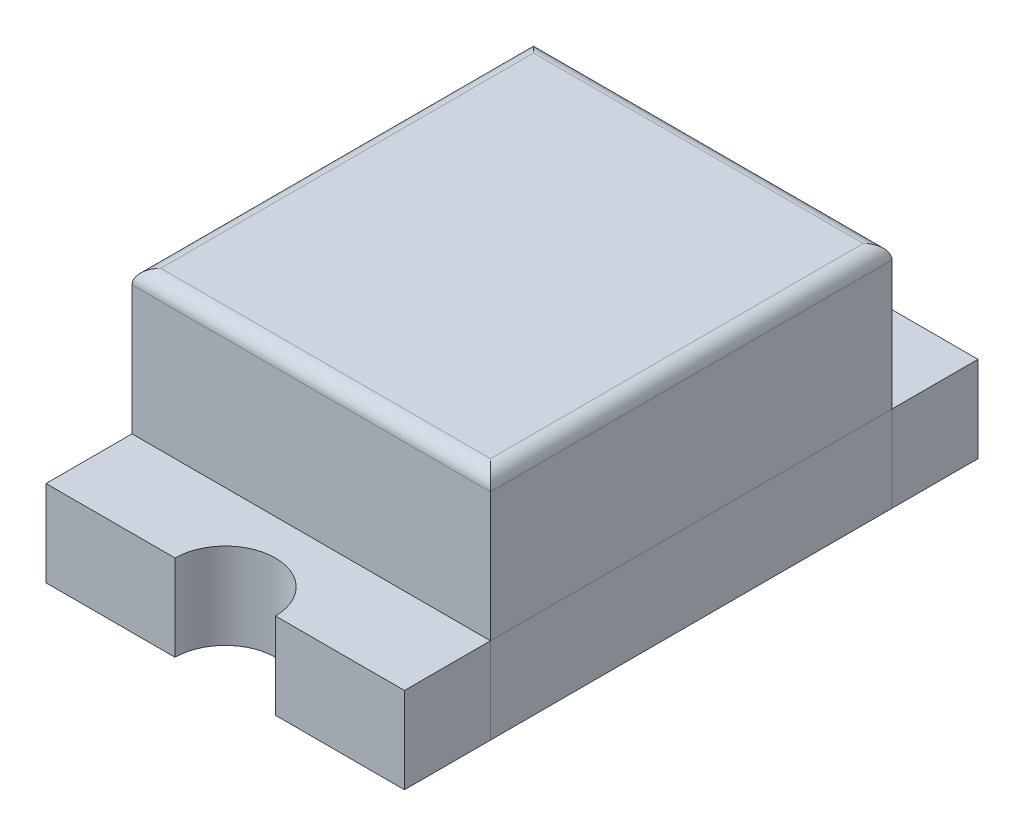
SolidWorks part; units mm, degrees
other "Saliente-Extruir4"
ref_plane "Alzado" through (0, 0, 0) normal (0, 0, 1) x (1, 0, 0)
ref_plane "Planta" through (0, 0, 0) normal (0, 1, 0) x (1, 0, 0)
ref_plane "Vista lateral" through (0, 0, 0) normal (1, 0, 0) x (0, 0, -1)
sketch "Croquis1" plane through (0, 0, 0) normal (0, 1, 0) x (1, 0, 0)
  line L0 (-0.8495, 0.7) -> (0.995, 0.7)
  line L1 (0.625, 1) -> (-0.625, 1)
  line L2 (0.625, 1) -> (0.625, -1)
  line L3 (0.625, -1) -> (-0.625, -1)
  line L4 (-0.625, 1) -> (-0.625, -1)
  line L5 (-0.8495, -0.7) -> (0.995, -0.7)
  circle A0 centre (0, 1) radius 0.175
  circle A1 centre (0, -1) radius 0.175
  point P0 (0, 0)
  point P14 (0, 0)
  dimension "D5" = 0.35
  dimension "D1" = 2
  dimension "D2" = 1.25
  dimension "D3" = 0.3
  dimension "D4" = 1.4
extrude "Saliente-Extruir1" add sketch "Croquis1" along normal blind 0.3 contours A0 L1 L4 L0 L2 | A1 L3 L2 L5 L4 region at (-0.6121, 0, -0.85) region at (0, 0, 0.7129)
extrude "Saliente-Extruir2" add sketch "Croquis1<4>" along normal blind 0.3 separate body contours L4 L5 L2 L0 region at (0, 0, 0)
sketch "Croquis1<4>" plane through (0, 0, 0) normal (0, 1, 0) x (1, 0, 0) same geometry as "Croquis1"
sketch "Croquis2" plane through (0, 0.3, 0) normal (0, 1, 0) x (1, 0, 0)
  line L1 (-0.625, 0.7) -> (0.625, 0.7)
  line L2 (-0.625, 0.7) -> (-0.625, -0.7)
  line L3 (-0.625, -0.7) -> (0.625, -0.7)
  line L4 (0.625, 0.7) -> (0.625, -0.7)
  point P0 (0, 0)
extrude "Saliente-Extruir3" add sketch "Croquis2" along normal blind 0.5 separate body contours L2 L1 L4 L3
fillet "Redondeo1" radius 0.05 4 edges at (-0.625, 0.8, 0) (0, 0.8, -0.7) (0.625, 0.8, 0) (0, 0.8, 0.7)
sketch "Croquis4" plane through (0, 0.3, 0) normal (0, 1, 0) x (1, 0, 0)
  line L7 (0.625, -1) -> (0.175, -1) construction
  line L8 (-0.1, -0.2) -> (0.1, -0.2)
  line L9 (-0.1, -0.2) -> (-0.1, 0)
  line L10 (-0.1, 0) -> (0.1, 0)
  line L11 (0.1, -0.2) -> (0.1, 0)
  point P0 (0, 0)
  point P6 (0, -0.1)
  dimension "D1" = 0.9
  dimension "D2" = 0.2
extrude "Saliente-Extruir7" add sketch "Croquis4" along normal blind 0.05 separate body
